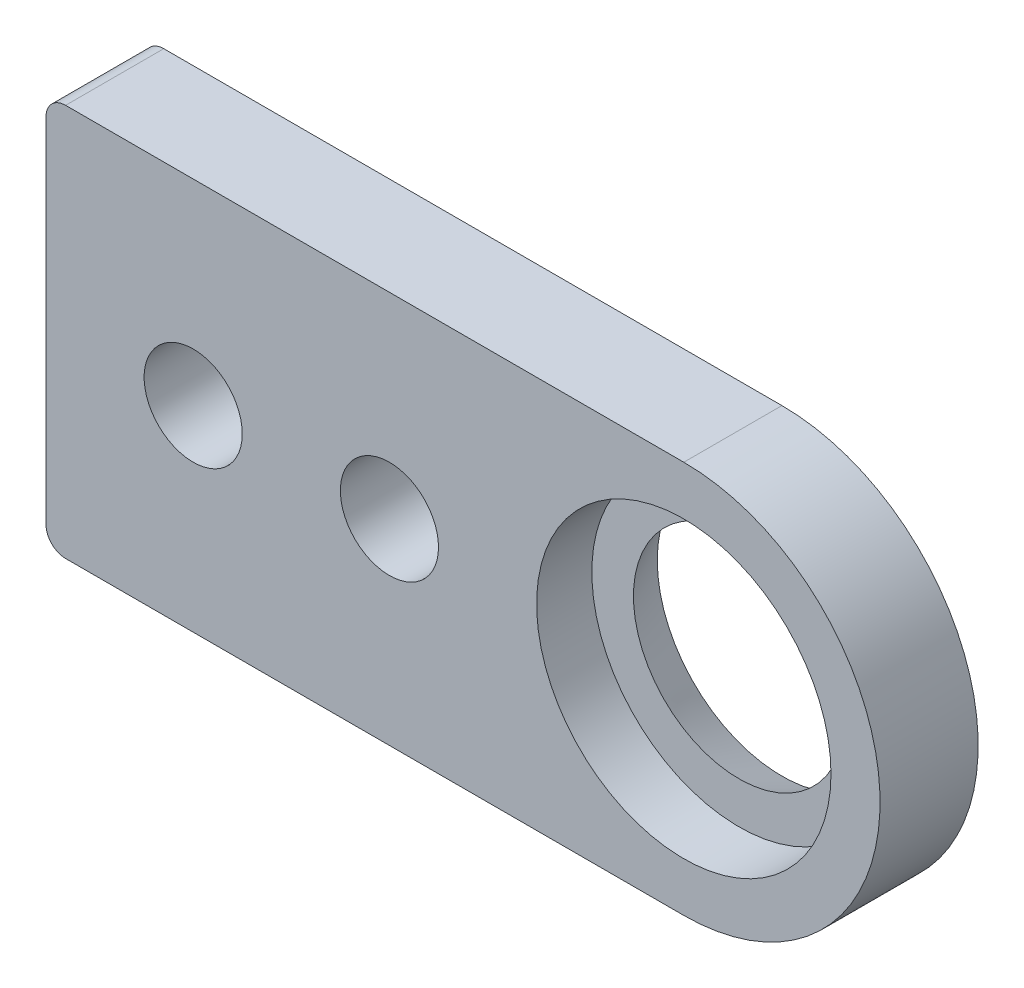
SolidWorks part; units mm, degrees
ref_plane "Front Plane" through (0, 0, 0) normal (0, 0, 1) x (1, 0, 0)
ref_plane "Top Plane" through (0, 0, 0) normal (0, 1, 0) x (1, 0, 0)
ref_plane "Right Plane" through (0, 0, 0) normal (1, 0, 0) x (0, 0, -1)
sketch "Sketch1" plane through (0, 0, 0) normal (0, 0, 1) x (1, 0, 0)
  line L0 (0, -12.7) -> (53.975, -12.7) construction
  line L1 (0, -25.4) -> (53.975, -25.4)
  line L2 (0, -25.4) -> (0, 0)
  line L3 (0, 0) -> (53.975, 0)
  line L4 (53.975, -25.4) -> (53.975, 0)
  circle A0 centre (41.275, -12.7) radius 9.525
  circle A1 centre (41.275, -12.7) radius 6.35
  circle A2 centre (9.525, -12.7) radius 3.175
  circle A3 centre (22.225, -12.7) radius 3.175
  point P0 (41.275, -12.7)
  dimension "D2" = 19.05
  dimension "D3" = 12.7
  dimension "D5" = 6.35
  dimension "D1" = 25.4
  dimension "D6" = 12.7
  dimension "D7" = 19.05
  dimension "D8" = 12.7
  dimension "D9" = 9.525
extrude "Boss-Extrude2" add sketch "Sketch1" along normal blind 6.35 contours L1 L4 L3 L2 A3 A2 A0 | L0 L2 L1 L4 A0 A3 A2 region at (23.6935, -5.397, 0) region at (23.6935, -20.003, 0)
extrude "Boss-Extrude3" add sketch "Sketch1<5>" along normal blind 2.7781 contours A0 A1 | L0 A0 A1 region at (41.275, -6.137, 0) region at (49.2125, -12.913, 0)
sketch "Sketch1<5>" plane through (0, 0, 0) normal (0, 0, 1) x (1, 0, 0) same geometry as "Sketch1"
fillet "Fillet1" radius 1.27 4 edges at (0, -25.4, 3.175) (0, 0, 3.175) (53.975, -25.4, 3.175) (53.975, 0, 3.175)
sketch "Sketch2" plane through (0, 0, 6.35) normal (0, 0, 1) x (1, 0, 0)
  line L0 (1.27, 0) -> (52.705, 0) construction
  line L1 (28.575, -25.4) -> (53.975, -25.4)
  line L2 (28.575, -25.4) -> (28.575, 0)
  line L3 (28.575, 0) -> (53.975, 0)
  line L4 (53.975, -25.4) -> (53.975, 0)
  line L5 (28.575, -25.4) -> (53.975, 0) construction
  line L6 (28.575, 0) -> (53.975, -25.4) construction
  circle A0 centre (41.275, -12.7) radius 12.7
  point P0 (41.275, -12.7)
  arc M12 (52.705, -25.4) -> (53.975, -24.13) centre (52.705, -24.13) ccw
  line M13 (53.975, -24.13) -> (53.975, -1.27)
  arc M14 (53.975, -1.27) -> (52.705, 0) centre (52.705, -1.27) ccw
  line M15 (52.705, 0) -> (1.27, 0)
extrude "Cut-Extrude1" cut sketch "Sketch2" against normal through all contours A0 L4 M14 M15 | A0 L1 M12 M13 region at (51.1124, -22.5374, 6.35) region at (51.1124, -2.8626, 6.35)
ref_axis "Axis1" through (41.275, -12.7, 2.7781) along (0, 0, -1)
ref_plane "Plane1" through (41.275, 0, 0) normal (1, 0, 0) x (0, 0, -1)
sketch "Sketch3" plane through (41.275, 0, 0) normal (1, 0, 0) x (0, 0, -1)
  line L0 (0, -12.7) -> (-6.35, -12.7)
  line L8 (0, -25.4) -> (0, 0) construction
  line L9 (-6.35, 0) -> (-6.35, -25.4) construction
  line L10 (-6.35, -12.7) -> (1.9474, -9.0058)
  line L11 (1.9474, -9.0058) -> (0, -4.6318)
  line L12 (0, -4.6318) -> (-8.2974, -8.326)
  line L13 (-8.2974, -8.326) -> (-6.35, -12.7)
  line L14 (0, -12.7) -> (0, -6.35)
  line L15 (0, -6.35) -> (-2.7781, -6.35)
  line L16 (-2.7781, -6.35) -> (-2.7781, -12.7)
  line L17 (0, -6.35) -> (0, -4.6318)
  line L18 (-2.7781, -6.35) -> (-2.7781, -5.8687)
  dimension "D1" = 4.7879
  dimension "D2" = 6.35
  dimension "D3" = 24
  dimension "D4" = 2.7781
revolve "Cut-Revolve3" cut sketch "Sketch3" angle 360 about axis through (41.275, -12.7, 2.7781) along (0, 0, -1) region at (41.275, -8.436, 1.4582) region at (41.275, -5.7422, 1.1287)
